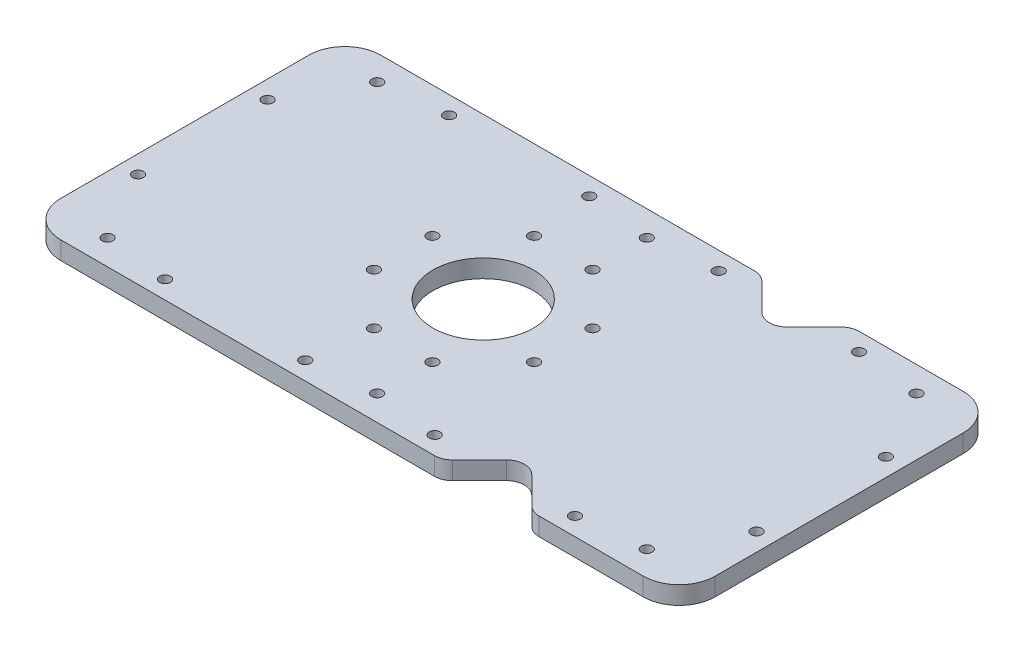
SolidWorks part; units mm, degrees
ref_plane "Front Plane" through (0, 0, 0) normal (0, 0, 1) x (1, 0, 0)
ref_plane "Top Plane" through (0, 0, 0) normal (0, 1, 0) x (1, 0, 0)
ref_plane "Right Plane" through (0, 0, 0) normal (1, 0, 0) x (0, 0, -1)
sketch "Sketch1" plane through (0, 0, 0) normal (0, 1, 0) x (1, 0, 0)
  line L0 (26.4645, -43.0355) -> (33.9645, -35.5355)
  line L1 (41.0355, -35.5355) -> (48.5355, -43.0355)
  line L2 (52.0711, -44.5) -> (81, -44.5)
  line L3 (91, -34.5) -> (91, 34.5)
  line L4 (81, 44.5) -> (52.0711, 44.5)
  line L5 (48.5355, 43.0355) -> (41.0355, 35.5355)
  line L6 (33.9645, 35.5355) -> (26.4645, 43.0355)
  line L7 (22.9289, 44.5) -> (-81, 44.5)
  line L8 (-91, 34.5) -> (-91, -34.5)
  line L9 (-81, -44.5) -> (22.9289, -44.5)
  arc A0 (22.9289, -44.5) -> (26.4645, -43.0355) centre (22.9289, -39.5) ccw
  arc A1 (41.0355, -35.5355) -> (33.9645, -35.5355) centre (37.5, -39.0711) ccw
  arc A2 (48.5355, -43.0355) -> (52.0711, -44.5) centre (52.0711, -39.5) ccw
  arc A3 (81, -44.5) -> (91, -34.5) centre (81, -34.5) ccw
  arc A4 (91, 34.5) -> (81, 44.5) centre (81, 34.5) ccw
  arc A5 (52.0711, 44.5) -> (48.5355, 43.0355) centre (52.0711, 39.5) ccw
  arc A6 (33.9645, 35.5355) -> (41.0355, 35.5355) centre (37.5, 39.0711) ccw
  arc A7 (26.4645, 43.0355) -> (22.9289, 44.5) centre (22.9289, 39.5) ccw
  arc A8 (-81, 44.5) -> (-91, 34.5) centre (-81, 34.5) ccw
  arc A9 (-91, -34.5) -> (-81, -44.5) centre (-81, -34.5) ccw
  circle A10 centre (-8, 0) radius 14
  circle A11 centre (-30.2739, 8.1317) radius 1.5
  circle A12 centre (-16.1317, 22.2739) radius 1.5
  circle A13 centre (0.1317, 22.2739) radius 1.5
  circle A14 centre (14.2739, 8.1317) radius 1.5
  circle A15 centre (14.2739, -8.1317) radius 1.5
  circle A16 centre (0.1317, -22.2739) radius 1.5
  circle A17 centre (-16.1317, -22.2739) radius 1.5
  circle A18 centre (-30.2739, -8.1317) radius 1.5
  circle A19 centre (-75, -37.5) radius 1.5
  circle A20 centre (-57, -39.5) radius 1.5
  circle A21 centre (-18, -39.5) radius 1.5
  circle A22 centre (0, -37.5) radius 1.5
  circle A23 centre (18, -39.5) radius 1.5
  circle A24 centre (57, -39.5) radius 1.5
  circle A25 centre (75, -37.5) radius 1.5
  circle A26 centre (86, -18) radius 1.5
  circle A27 centre (86, 18) radius 1.5
  circle A28 centre (75, 37.5) radius 1.5
  circle A29 centre (57, 39.5) radius 1.5
  circle A30 centre (18, 39.5) radius 1.5
  circle A31 centre (0, 37.5) radius 1.5
  circle A32 centre (-18, 39.5) radius 1.5
  circle A33 centre (-57, 39.5) radius 1.5
  circle A34 centre (-75, 37.5) radius 1.5
  circle A35 centre (-86, 18) radius 1.5
  circle A36 centre (-86, -18) radius 1.5
extrude "Boss-Extrude1" add sketch "Sketch1" along normal blind 5
sketch "Sketch2" plane through (0, 0, 0) normal (0, 1, 0) x (1, 0, 0)
  line L0 (0, 0) -> (-142.7211, 0) construction
ref_axis "Axis1" through (-8, 0, 0) along (0, 1, 0)
